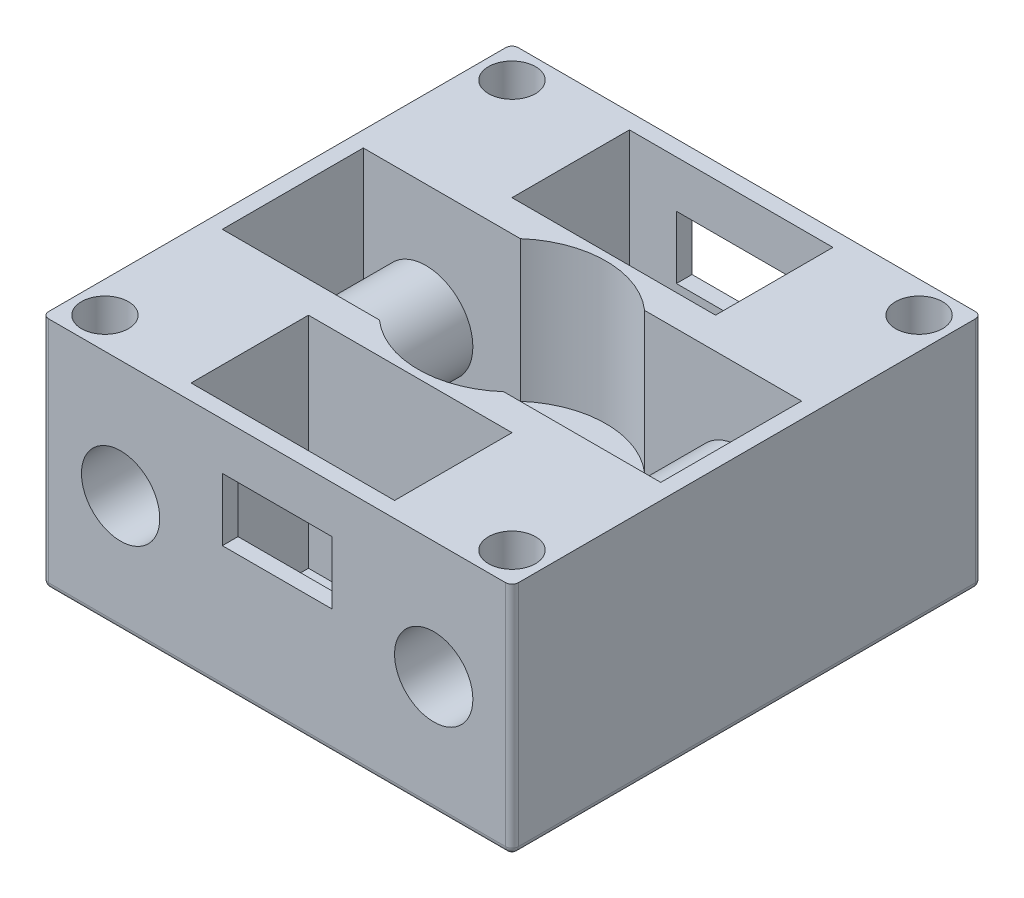
SolidWorks part; units mm, degrees
ref_plane "前视基准面" through (0, 0, 0) normal (0, 0, 1) x (1, 0, 0)
ref_plane "上视基准面" through (0, 0, 0) normal (0, 1, 0) x (1, 0, 0)
ref_plane "右视基准面" through (0, 0, 0) normal (1, 0, 0) x (0, 0, -1)
sketch "草图2" plane through (0, 0, 0) normal (0, 1, 0) x (1, 0, 0)
  line L1 (-7.5, -7.5) -> (7.5, -7.5)
  line L2 (-7.5, -7.5) -> (-7.5, 7.5)
  line L3 (-7.5, 7.5) -> (7.5, 7.5)
  line L4 (7.5, -7.5) -> (7.5, 7.5)
extrude "凸台-拉伸1" add sketch "草图2" along normal blind 7.5
sketch "草图3" plane through (0, 7.5, 0) normal (0, 1, 0) x (-1, 0, 0)
  line L1 (7, 2.25) -> (-7, 2.25)
  line L2 (7, 2.25) -> (7, -2.25)
  line L3 (7, -2.25) -> (-7, -2.25)
  line L4 (-7, 2.25) -> (-7, -2.25)
extrude "切除-拉伸1" cut sketch "草图3" against normal blind 7
sketch "草图4" plane through (0, 7.5, 0) normal (0, 1, 0) x (1, 0, 0)
  circle A0 centre (0, 0) radius 3
extrude "切除-拉伸2" cut sketch "草图4" against normal blind 4.5
sketch "草图5" plane through (0, 7.5, 0) normal (0, 1, 0) x (-1, 0, 0)
  line L0 (7.9075, 0) -> (-8.3479, 0) construction
  line L1 (3.25, -3.25) -> (-3.25, -3.25)
  line L2 (3.25, -3.25) -> (3.25, -7)
  line L3 (3.25, -7) -> (-3.25, -7)
  line L4 (-3.25, -3.25) -> (-3.25, -7)
  line L5 (-3.25, 3.25) -> (-3.25, 7)
  line L6 (3.25, 7) -> (-3.25, 7)
  line L7 (3.25, 3.25) -> (3.25, 7)
  line L8 (3.25, 3.25) -> (-3.25, 3.25)
extrude "切除-拉伸3" cut sketch "草图5" against normal blind 7
sketch "草图6" plane through (0, 0, 7.5) normal (0, 0, 1) x (1, 0, 0)
  circle A0 centre (-5, 3.75) radius 1.5
  circle A1 centre (5, 3.75) radius 1.5
extrude "凸台-拉伸2" add sketch "草图6" against normal through all
sketch "草图7" plane through (0, 0, 7.5) normal (0, 0, 1) x (1, 0, 0)
  circle A0 centre (-5, 3.75) radius 1.25
  circle A1 centre (5, 3.75) radius 1.25
extrude "切除-拉伸4" cut sketch "草图7" against normal through all
sketch "草图8" plane through (0, 0, 0) normal (0, -1, 0) x (1, 0, 0)
  line L1 (-1.5, -1.5) -> (1.5, -1.5)
  line L2 (-1.5, -1.5) -> (-1.5, 1.5)
  line L3 (-1.5, 1.5) -> (1.5, 1.5)
  line L4 (1.5, -1.5) -> (1.5, 1.5)
extrude "凸台-拉伸3" add sketch "草图8" along normal blind 1
sketch "草图9" plane through (0, 0, 7.5) normal (0, 0, 1) x (1, 0, 0)
  line L1 (-1.75, 6) -> (1.75, 6)
  line L2 (-1.75, 6) -> (-1.75, 4)
  line L3 (-1.75, 4) -> (1.75, 4)
  line L4 (1.75, 6) -> (1.75, 4)
extrude "切除-拉伸5" cut sketch "草图9" against normal up to next
extrude "切除-拉伸6" cut sketch "草图9<2>" along normal up to next from offset 15 offset against normal yes
sketch "草图9<2>" plane through (0, 0, 7.5) normal (0, 0, 1) x (1, 0, 0) same geometry as "草图9"
sketch "草图10" plane through (0, 0, 0) normal (0, 0, 1) x (1, 0, 0)
  line L0 (-1.95, -2.5) -> (1.95, -2.5)
  line L1 (-1.95, -2.5) -> (-1.95, -1.5556)
  line L2 (1.95, -2.5) -> (1.95, -1.5556)
  line L4 (-1.5, -1) -> (-1.5, 0) construction
  line L5 (-1.5, -0.6771) -> (1.5, -0.6771)
  arc A0 (-1.5, -0.6771) -> (-1.95, -1.5556) centre (0, -2) ccw
  arc A3 (1.95, -1.5556) -> (1.5, -0.6771) centre (0, -2) ccw
extrude "凸台-拉伸4" add sketch "草图10" along normal blind 2 and the other way blind 2
sketch "草图11" plane through (0, 0, 0) normal (1, 0, 0) x (0, 0, -1)
  line L0 (1.95, -2.5) -> (1.95, -1.5556)
  line L1 (-1.95, -2.5) -> (-1.95, -1.5556)
  line L2 (2, -2.5) -> (1.95, -2.5)
  line L3 (-2, -2.5) -> (-2, -0.6771)
  line L4 (-2, -0.6771) -> (-1.5, -0.6771)
  line L5 (2, -0.6771) -> (2, -2.5)
  line L6 (-1.95, -2.5) -> (-2, -2.5)
  line L7 (1.5, -0.6771) -> (2, -0.6771)
  arc A0 (-1.5, -0.6771) -> (-1.95, -1.5556) centre (0, -2) ccw
  arc A1 (1.95, -1.5556) -> (1.5, -0.6771) centre (0, -2) ccw
extrude "切除-拉伸7" cut sketch "草图11" against normal up to next and the other way up to next
fillet "圆角1" radius 0.1 4 edges at (0, -2.5, -1.95) (-1.95, -2.5, 0) (0, -2.5, 1.95) (1.95, -2.5, 0)
fillet "圆角2" radius 0.2 8 edges at (-7.5, 3.75, -7.5) (7.5, 3.75, -7.5) (-7.5, 3.75, 7.5) (-7.5, 0, 0) (0, 0, -7.5) (7.5, 0, 0) (0, 0, 7.5) (7.5, 3.75, 7.5)
sketch "草图12" plane through (0, 7.5, 0) normal (0, 1, 0) x (-1, 0, 0)
  circle A0 centre (6.5, -6.5) radius 0.75
  circle A1 centre (-6.5, 6.5) radius 0.75
  circle A2 centre (6.5, 6.5) radius 0.75
  circle A3 centre (-6.5, -6.5) radius 0.75
extrude "切除-拉伸8" cut sketch "草图12" against normal blind 2
